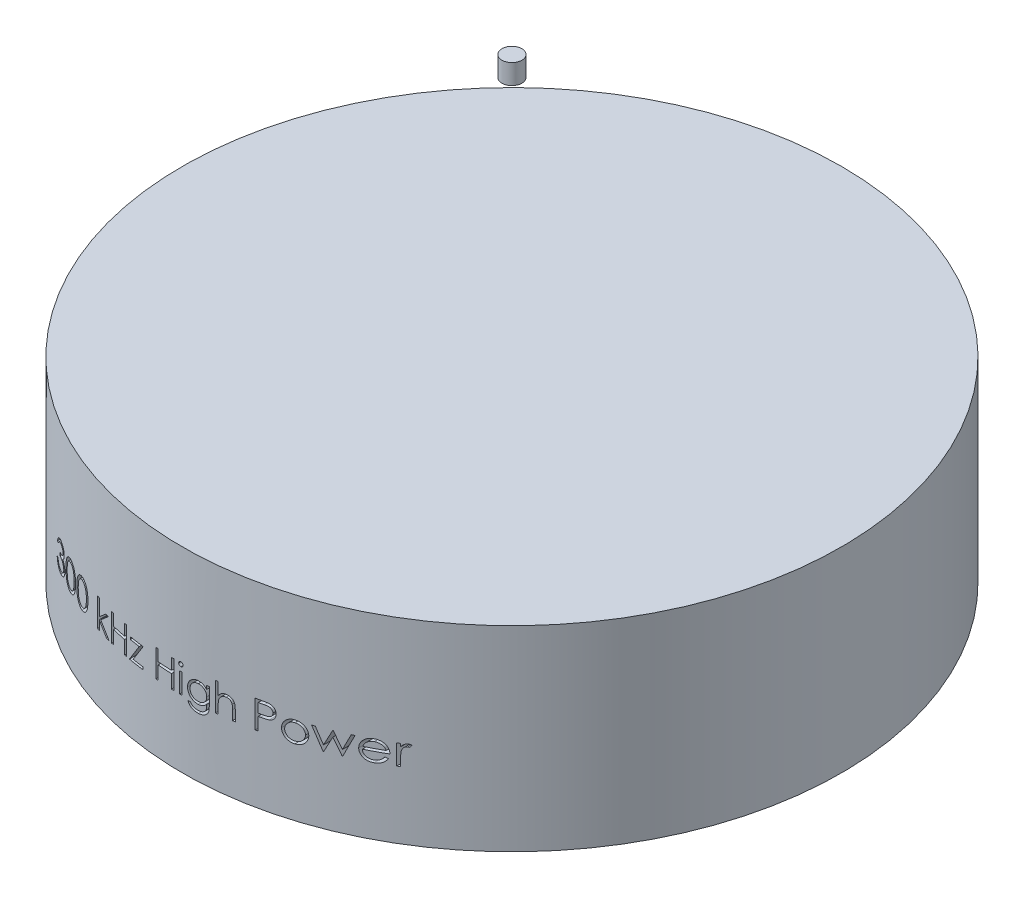
SolidWorks part; units mm, degrees
ref_plane "Front Plane" through (0, 0, 0) normal (0, 0, 1) x (1, 0, 0)
ref_plane "Top Plane" through (0, 0, 0) normal (0, 1, 0) x (1, 0, 0)
ref_plane "Right Plane" through (0, 0, 0) normal (1, 0, 0) x (0, 0, -1)
sketch "Sketch1" plane through (0, 0, 0) normal (0, 0, 1) x (1, 0, 0)
  line L0 (0, 0) -> (0, 29.7209) construction
  line L2 (0, 0) -> (41.9, 0)
  line L3 (0, 0) -> (0, 24.892)
  line L4 (0, 24.892) -> (41.9, 24.892)
  line L5 (41.9, 0) -> (41.9, 24.892)
  dimension "D1" = 83.8
  dimension "D2" = 24.892
revolve "Revolve1" add sketch "Sketch1" angle 360 about L0
sketch "Sketch2" plane through (0, 0, 0) normal (1, 0, 0) x (0, 0, -1)
  line L0 (0, 0) -> (0, 89.4138) construction
  line L1 (41.9, 24.892) -> (-41.9, 24.892) construction
  line L2 (0, 58.166) -> (-1.27, 58.166)
  line L3 (0, 58.166) -> (0, 55.626)
  line L4 (0, 55.626) -> (-1.27, 55.626)
  line L5 (-1.27, 58.166) -> (-1.27, 55.626)
  dimension "D1" = 1.27
  dimension "D2" = 2.54
  dimension "D3" = 30.734
revolve "Revolve2" add sketch "Sketch2" angle 360 about L0
sketch "Sketch3" plane through (0, 0, 0) normal (0, 0, 1) x (1, 0, 0)
  line L0 (-41.9, 8.5239) -> (41.9, 8.5239) construction
  line L1 (-41.9, 24.892) -> (-41.9, 0) construction
  line L2 (41.9, 0) -> (41.9, 24.892) construction
  text T0 "300 kHz High Power"
extrude "Cut-Extrude1" cut sketch "Sketch3" against normal blind 12.7 from offset 43.18
